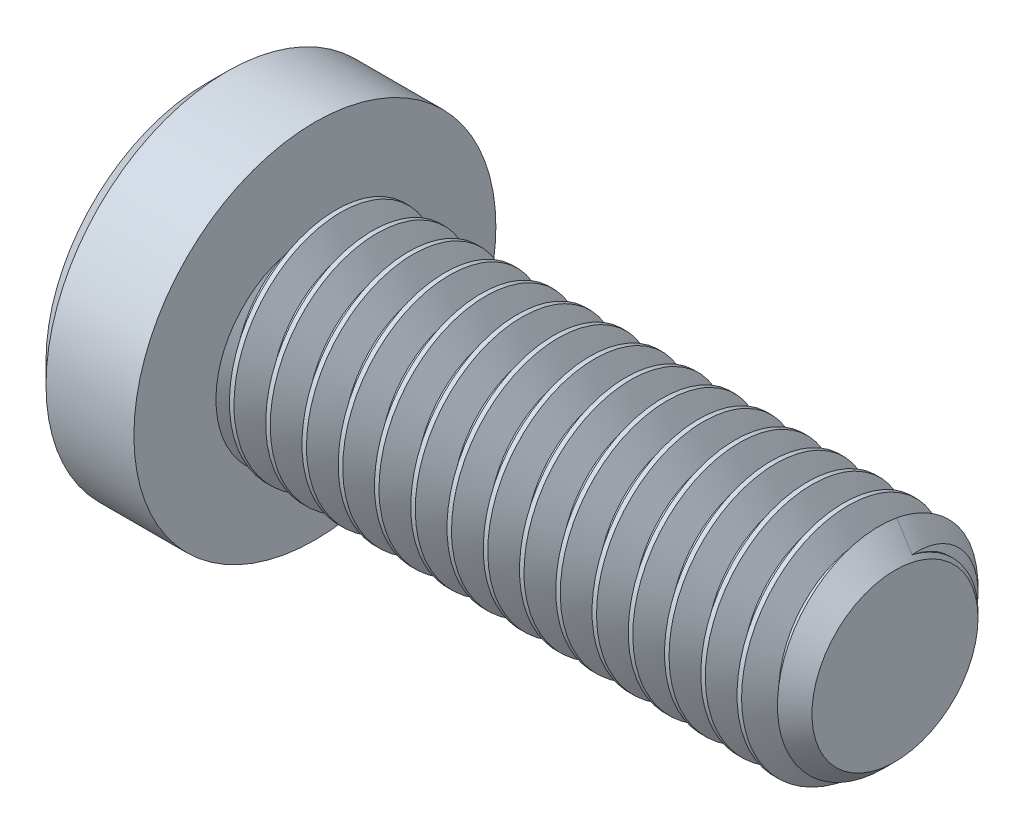
SolidWorks part; units mm, degrees
ref_plane "Front Plane" through (0, 0, 0) normal (0, 0, 1) x (1, 0, 0)
ref_plane "Top Plane" through (0, 0, 0) normal (0, 1, 0) x (1, 0, 0)
ref_plane "Right Plane" through (0, 0, 0) normal (1, 0, 0) x (0, 0, -1)
sketch "Sketch1" plane through (0, 0, 0) normal (0, 0, 1) x (1, 0, 0)
  line L0 (6.35, 0) -> (-6.35, 0) construction
  line L1 (6.35, 2.413) -> (6.35, -2.413) construction
  line L2 (-6.35, 3.9624) -> (-6.35, -3.9624) construction
  line L3 (-6.35, 3.9624) -> (-8.274, 3.9624) construction
  line L4 (-8.274, 3.9624) -> (-8.7312, 3.5052) construction
  line L5 (-8.7312, 3.5052) -> (-8.7312, -3.5052) construction
  line L6 (-8.7312, -3.5052) -> (-8.274, -3.9624) construction
  line L7 (-8.274, -3.9624) -> (-6.35, -3.9624) construction
  point P7 (-6.9024, 0)
  point P12 (3.175, -2.413)
  dimension "D1" = 45
  dimension "Dec." = 4.826
  dimension "Length" = 12.7
  dimension "Head Dia" = 7.9248
  dimension "Head Height" = 2.3813
  dimension "Hex Depth" = 1.8288
  dimension "Chamfer" = 0.4572
  dimension "D2" = 3.175
ref_plane "Plane1" through (6.35, 0, 0) normal (1, 0, 0) x (0, 0, -1)
ref_plane "Plane2" through (-8.7312, 0, 0) normal (1, 0, 0) x (0, 0, -1)
sketch "Sketch2" plane through (6.35, 0, 0) normal (1, 0, 0) x (0, 0, -1)
  circle A0 centre (0, 0) radius 2.413
extrude "Boss-Extrude1" add sketch "Sketch2" against normal up to vertex (12.7 mm away) up to point (-6.35, 0, 0)
sketch "Sketch3" plane through (6.35, 0, 0) normal (1, 0, 0) x (0, 0, -1)
  circle A0 centre (0, 0) radius 2.413 construction
  circle A1 centre (0, 0) radius 2.413
curve "Helix/Spiral1" pitch 0.7937 height 13.4937 radius 2.413 centre (6.35, 0, 0) axis (-1, 0, 0) start towards (0, 1, 0) parameters "Pitch"=0.7937
chamfer "Chamfer1" distance 0.5953 angle 45 1 edges at (6.35, 0, -2.413)
sketch "Sketch5" plane through (0, 0, 0) normal (0, 0, 1) x (1, 0, 0)
  line L0 (6.0027, 2.413) -> (6.6973, 2.413)
  line L1 (6.6973, 2.413) -> (6.3996, 1.8974)
  line L2 (6.3996, 1.8974) -> (6.3004, 1.8974)
  line L3 (6.3004, 1.8974) -> (6.0027, 2.413)
  line L4 (6.35, 1.8974) -> (6.35, 2.413) construction
  line L5 (6.1516, 2.1552) -> (6.5484, 2.1552) construction
  dimension "D1" = 60
  dimension "D2" = 0.3969
  dimension "D3" = 0.0992
sweep "Cut-Sweep1" cut profiles "Sketch5" path "Helix/Spiral1" align with end faces yes
sketch "Sketch4" plane through (-8.7312, 0, 0) normal (1, 0, 0) x (0, 0, -1)
  line L0 (-3.9624, 0.7937) -> (3.9624, 0.7937) construction
  line L1 (0, 1.3748) -> (-1.1906, 0.6874)
  line L2 (-1.1906, 0.6874) -> (-1.1906, -0.6874)
  line L3 (-1.1906, -0.6874) -> (0, -1.3748)
  line L4 (0, -1.3748) -> (1.1906, -0.6874)
  line L5 (1.1906, -0.6874) -> (1.1906, 0.6874)
  line L6 (1.1906, 0.6874) -> (0, 1.3748)
  line L7 (0, 0) -> (0, 0.7937) construction
  circle A0 centre (0, 0) radius 1.1906 construction
  dimension "Hex Size" = 2.3813
  dimension "D1" = 7.9248
  dimension "D2" = 0.7937
sketch "Sketch6" plane through (0, 0, 0) normal (0, 0, 1) x (1, 0, 0)
  line L0 (-8.274, 3.9624) -> (-8.7312, 3.5052) construction
  line L1 (-6.35, 3.9624) -> (-8.274, 3.9624) construction
  line L2 (-6.35, 3.9624) -> (-6.35, -3.9624) construction
  line L3 (-8.7312, 3.5052) -> (-8.7312, -3.5052) construction
  line L4 (-8.274, 3.9624) -> (-8.7312, 3.5052)
  line L5 (-6.35, 3.9624) -> (-8.274, 3.9624)
  line L6 (-6.35, 3.9624) -> (-6.35, 0)
  line L7 (-8.7312, 3.5052) -> (-8.7312, 0)
  line L8 (-6.35, 0) -> (-8.7312, 0) construction
  line L9 (-6.35, 0) -> (-8.7312, 0)
revolve "Revolve1" add sketch "Sketch6" angle 360 about L8
extrude "Cut-Extrude1" cut sketch "Sketch4" along normal up to vertex (1.8288 mm away) up to point (-6.9024, 0, 0)
sketch "Sketch8" plane through (-8.7312, 0, 0) normal (-1, 0, 0) x (0, 0, 1)
  circle A1 centre (0, 0) radius 1.3748
extrude "Cut-Extrude2" cut sketch "Sketch8" against normal through all draft 45
equation "\"D3@Helix/Spiral1\" = \"Length@Sketch1\"+\"Pitch@Helix/Spiral1\""
equation "\"D3@Sketch5\" = \"Pitch@Helix/Spiral1\"*.125"
equation "\"D2@Sketch5\" = \"Pitch@Helix/Spiral1\"*.50"
equation "\"D1@Chamfer1\" = \"Pitch@Helix/Spiral1\"*.75"
equation "\"D2@Sketch1\" = \"Pitch@Helix/Spiral1\"*4"
equation "\"D1@Sketch4\" = \"Head Dia@Sketch1\""
